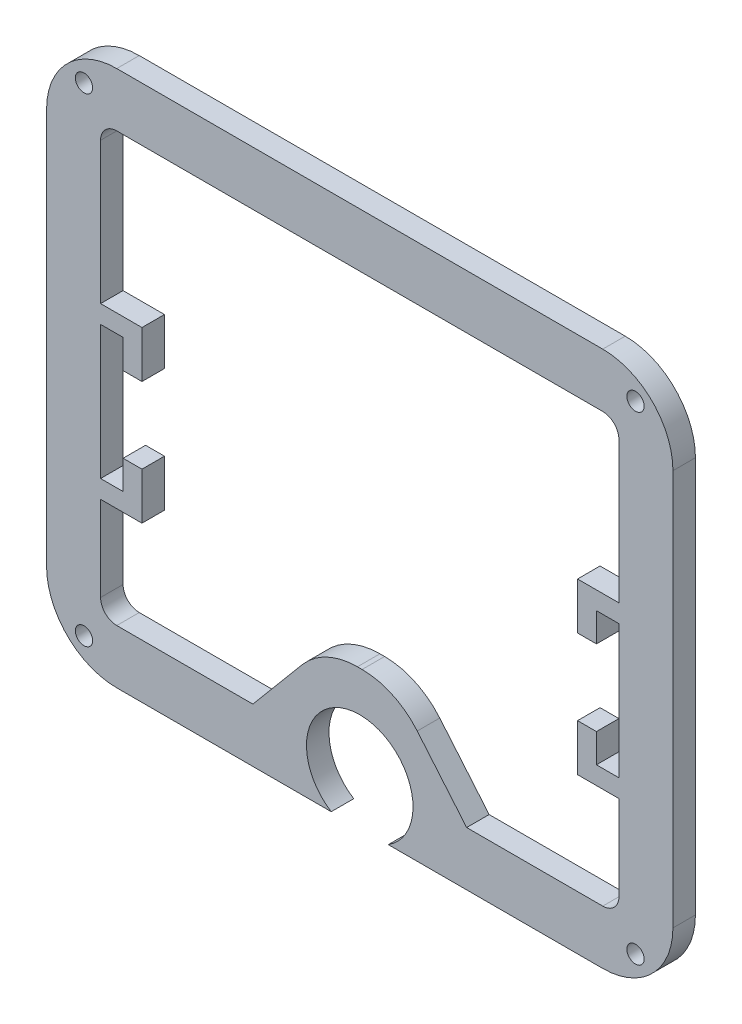
SolidWorks part; units mm, degrees
material "Delrin"
ref_plane "Front Plane" through (0, 0, 0) normal (0, 0, 1) x (1, 0, 0)
ref_plane "Top Plane" through (0, 0, 0) normal (0, 1, 0) x (1, 0, 0)
ref_plane "Right Plane" through (0, 0, 0) normal (1, 0, 0) x (0, 0, -1)
sketch "Sketch1" plane through (0, 0, 0) normal (0, 0, 1) x (1, 0, 0)
  line L0 (-17.145, -18.923) -> (-2.0127, -18.923)
  line L1 (-18.288, 13.97) -> (-18.288, -13.97)
  line L2 (-17.145, -15.113) -> (-7.5425, -15.113)
  line L3 (7.5425, -15.113) -> (17.145, -15.113)
  line L4 (18.288, 13.97) -> (18.288, -13.97)
  line L5 (-1000, 0) -> (49000, 0) construction
  line L7 (2.0127, -18.923) -> (17.145, -18.923)
  line L8 (17.145, 15.113) -> (-17.145, 15.113)
  line L9 (-7.5425, -15.113) -> (-4.0566, -10.9586)
  line L10 (-22.098, 13.97) -> (-22.098, -13.97)
  line L11 (7.5425, -15.113) -> (4.0566, -10.9586)
  line L12 (-0.1651, -9.144) -> (0.1651, -9.144)
  line L13 (22.098, 13.97) -> (22.098, -13.97)
  line L14 (17.145, 18.923) -> (-17.145, 18.923)
  line L18 (0, 12.5532) -> (0, -24.2768) construction
  arc A0 (2.0127, -18.923) -> (-2.0127, -18.923) centre (0, -15.748) ccw
  arc A1 (-17.145, -15.113) -> (-18.288, -13.97) centre (-17.145, -13.97) cw
  arc A2 (-0.1651, -9.144) -> (-4.0566, -10.9586) centre (-0.1651, -14.224) ccw
  arc A3 (18.288, -13.97) -> (17.145, -15.113) centre (17.145, -13.97) cw
  arc A4 (17.145, 15.113) -> (18.288, 13.97) centre (17.145, 13.97) cw
  arc A5 (-17.145, -18.923) -> (-22.098, -13.97) centre (-17.145, -13.97) cw
  arc A6 (22.098, -13.97) -> (17.145, -18.923) centre (17.145, -13.97) cw
  arc A7 (17.145, 18.923) -> (22.098, 13.97) centre (17.145, 13.97) cw
  arc A8 (-17.145, 18.923) -> (-22.098, 13.97) centre (-17.145, 13.97) ccw
  circle A9 centre (-19.4575, 16.891) radius 0.6096
  circle A10 centre (19.4575, 16.891) radius 0.6096
  arc A11 (-17.145, 15.113) -> (-18.288, 13.97) centre (-17.145, 13.97) ccw
  arc A12 (0.1651, -9.144) -> (4.0566, -10.9586) centre (0.1651, -14.224) cw
  circle A13 centre (19.4575, -16.891) radius 0.6096
  circle A14 centre (-19.4575, -16.891) radius 0.6096
  arc A18 (7.5425, -15.113) -> (-7.5425, -15.113) centre (0, -15.748) ccw construction
  point P0 (0, 0)
  dimension "D4" = 3.175
  dimension "D6" = 37.846
  dimension "D7" = 44.196
  dimension "D8" = 3.81
  dimension "D9" = 6.604
  dimension "D5" = 1.2192
  dimension "D2" = 4.953
  dimension "D3" = 7.5184
  dimension "D10" = 5.08
  dimension "D11" = 5.08
  dimension "D12" = 16.891
  dimension "D13" = 19.4575
extrude "Boss-Extrude1" add sketch "Sketch1" along normal blind 1.5875
sketch "Sketch2" plane through (-18.288, 0, 0) normal (1, 0, 0) x (0, 0, -1)
  line L0 (0, 2.7178) -> (-1.5875, 2.7178)
  line L1 (0, -6.701) -> (-1.5875, -6.701) construction
  line L2 (-1.5875, -15.113) -> (0, -15.113)
  line L3 (-1.5875, -15.113) -> (0, -15.113) construction
  line L4 (0, -13.97) -> (0, 13.97)
  line L5 (0, 13.97) -> (-1.5875, 13.97)
  line L6 (-1.5875, 13.97) -> (-1.5875, -13.97)
  line L7 (0, 13.97) -> (-1.5875, 13.97)
  line L8 (0, -13.97) -> (0, 3.9878)
  line L9 (-1.5875, -15.113) -> (-1.5875, -7.971)
  line L10 (-1.5875, 3.9878) -> (-1.5875, -13.97)
  line L11 (-1.5875, -13.97) -> (0, -13.97)
  line L12 (0, -15.113) -> (0, -7.971)
  line L13 (0, 3.9878) -> (-1.5875, 3.9878)
  line L14 (-1.5875, 2.7178) -> (-1.5875, -6.6447)
  line L15 (-1.5875, 3.9878) -> (-1.5875, 2.7178)
  line L16 (0, 2.7178) -> (0, 3.9878)
  line L17 (0, -7.9147) -> (0, 1.4693)
  line L18 (-1.5875, -7.9147) -> (-1.5875, -6.6447)
  line L19 (0, -6.701) -> (-1.5875, -6.701)
  line L21 (0, -7.971) -> (-1.5875, -7.971)
  line L22 (0, -7.971) -> (0, -13.97)
  line L23 (-1.5875, -7.971) -> (-1.5875, -13.97)
  line L24 (47.9467, 2.7178) -> (-14.2384, 2.7178) construction
  line L28 (-1.5875, -13.97) -> (0, -13.97)
  line L29 (47.5364, -9.8164) -> (-14.2384, -5.7678) construction
  line M5 (0, -13.97) -> (0, 13.97)
  line M7 (-1.5875, 13.97) -> (-1.5875, -13.97)
  dimension "D1" = 0
  dimension "D2" = 1.27
  dimension "D4" = 1.27
extrude "Boss-Extrude2" add sketch "Sketch2" along normal blind 2.921 contours L13 L10 L0 M5 | L19 L17 L8 L0 L10 M7 | L21 L8 L19 L18 M5 M7 region at (-18.288, -1.9916, 0.7937) region at (-18.288, 3.3528, 0.7937) region at (-18.288, -7.336, 0.7937)
extrude "Cut-Extrude1" cut sketch "Sketch2<3>" along normal blind 1.5875 contours L19 L8 L10 region at (-18.288, -1.9916, 0.7937)
sketch "Sketch2<3>" plane through (-18.288, 0, 0) normal (1, 0, 0) x (0, 0, -1) same geometry as "Sketch2"
sketch "Sketch3" plane through (-16.7005, 0, 0) normal (-1, 0, 0) x (0, 0, 1)
  line L0 (0, 2.7178) -> (1.5875, 2.7178) construction
  line L1 (0, -6.701) -> (1.5875, -6.701) construction
  line L2 (0, 2.7178) -> (1.5875, 2.7178)
  line L3 (0, -6.701) -> (1.5875, -6.701)
  line L4 (0, 0.6858) -> (1.5875, 0.6858)
  line L5 (0, -4.669) -> (1.5875, -4.669)
  line L6 (1.5875, 0.6858) -> (1.5875, -4.669)
  line L7 (0, -4.669) -> (0, 0.6858)
  line M2 (1.5875, -6.701) -> (1.5875, 2.7178)
  line M4 (0, 2.7178) -> (0, -6.701)
  dimension "D1" = 2.032
  dimension "D2" = 2.032
extrude "Cut-Extrude2" cut sketch "Sketch3" against normal up to surface (1.3335 mm away) contours L5 L4 M4 M2 region at (-16.7005, -1.9916, 0.7937) up to face at (-15.367, -1.9916, 0.7937)
mirror "Mirror1" about plane through (0, 0, 0) normal (1, 0, 0) of "Cut-Extrude2", "Boss-Extrude2", "Cut-Extrude1"
